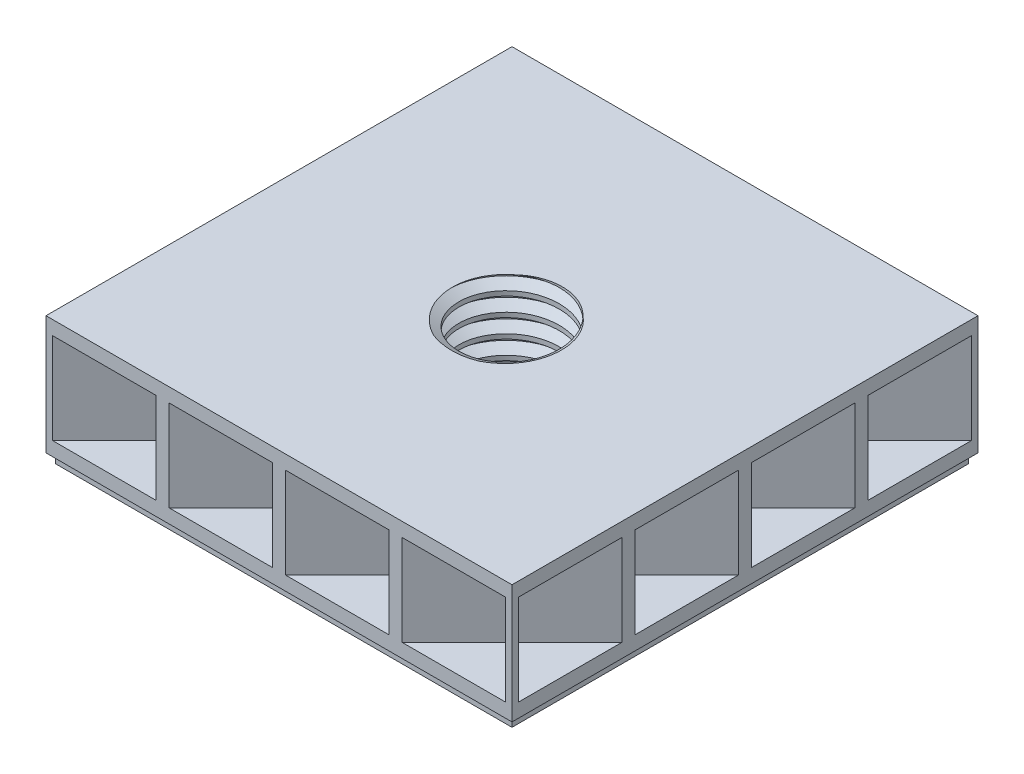
SolidWorks part; units mm, degrees
ref_plane "Front Plane" through (0, 0, 0) normal (0, 0, 1) x (1, 0, 0)
ref_plane "Top Plane" through (0, 0, 0) normal (0, 1, 0) x (1, 0, 0)
ref_plane "Right Plane" through (0, 0, 0) normal (1, 0, 0) x (0, 0, -1)
sketch "Sketch1" plane through (0, 0, 0) normal (0, 1, 0) x (1, 0, 0)
  line L0 (0, 20) -> (20, 0) construction
  line L1 (0, 0) -> (20, 0)
  line L2 (0, 0) -> (0, 20)
  line L3 (0, 20) -> (20, 20)
  line L4 (20, 0) -> (20, 20)
  circle A0 centre (10, 10) radius 2.157
  point P5 (10, 10)
  dimension "D3" = 4.314
  dimension "D1" = 20
  dimension "D2" = 20
extrude "Main Square" add sketch "Sketch1" along normal blind 5.5 contours L3 L0 A0 L4 | L0 L2 L1 A0
sketch "Sketch2" plane through (0, 0, 0) normal (0, 0, 1) x (1, 0, 0)
  line L0 (10, 5.5) -> (10, 0) construction
  line L1 (0, 0) -> (20, 0) construction
  line L3 (0, 0.4) -> (0.2, 0.4)
  line L4 (0, 5.5) -> (0, 0) construction
  line L5 (0.2, 0.4) -> (0.2, 0)
  line L6 (0.2, 0) -> (0, 0)
  line L7 (0, 0) -> (0, 0.4)
  line L8 (20, 0) -> (20, 0.4)
  line L9 (19.8, 0) -> (20, 0)
  line L10 (19.8, 0.4) -> (19.8, 0)
  line L11 (20, 0.4) -> (19.8, 0.4)
  point P2 (0, 0)
  point P3 (0, 0)
  point P4 (0, 0)
  point P5 (10, 0)
  point P17 (0, 0)
  point P18 (0, 0)
  point P19 (0, 0)
  point P20 (0, 0)
  point P21 (0, 0)
  point P22 (0, 0)
  dimension "D1" = 0.4
  dimension "D2" = 0.2
extrude "AntiWarpCuts1" cut sketch "Sketch2" against normal through all both and the other way through all
sketch "Sketch3" plane through (0, 0, 0) normal (-1, 0, 0) x (0, 0, 1)
  line L0 (-10, 5.5) -> (-10, 0) construction
  line L3 (-0.2, 0) -> (-0.2, 0.4)
  line L4 (-20, 0) -> (-19.8, 0)
  line L5 (-20, 0) -> (-20, 0.4)
  line L6 (-20, 0.4) -> (-19.8, 0.4)
  line L7 (-19.8, 0) -> (-19.8, 0.4)
  line L8 (0, 0.4) -> (-0.2, 0.4)
  line L9 (0, 0) -> (0, 0.4)
  line L10 (0, 0) -> (-0.2, 0)
  point P2 (0, 0)
  point P3 (-20, 0)
  point P4 (0, 0)
  point P5 (0, 0)
  point P15 (0, 0)
  dimension "D1" = 0.2
  dimension "D2" = 0.4
extrude "AntiWarpCuts2" cut sketch "Sketch3" against normal through all both and the other way through all
sketch "Sketch5" plane through (0, 0, 0) normal (-1, 0, 0) x (0, 0, 1)
  line L0 (-20, 5.5) -> (-20, 0.4) construction
  line L1 (-20, 4.9) -> (0, 4.9)
  line L2 (-20, 4.9) -> (-20, 1)
  line L3 (-20, 1) -> (0, 1)
  line L4 (0, 4.9) -> (0, 1)
  line L5 (0, 5.5) -> (0, 0.4) construction
  line L6 (0, 5.5) -> (-20, 5.5) construction
  line L7 (-20, 0.4) -> (0, 0.4) construction
  dimension "D1" = 0.6
  dimension "D2" = 0.6
extrude "NoFill" cut sketch "Sketch5" against normal through all both and the other way through all
sketch "Sketch6" plane through (0, 1, 0) normal (0, 1, 0) x (1, 0, 0)
  circle A0 centre (10, 10) radius 4
  circle A1 centre (10, 10) radius 2.157
  dimension "D1" = 8
extrude "ThreadMe" add sketch "Sketch6" along normal up to next contours A0
sketch "Sketch7" plane through (0, 4.9, 0) normal (0, -1, 0) x (1, 0, 0)
  line L0 (0, -5) -> (5, -5) construction
  line L1 (0, -20) -> (0, 0) construction
  line L2 (5, -5) -> (5, 0) construction
  line L3 (0, 0) -> (20, 0) construction
  line L4 (2.5, -2.5) -> (5, 0) construction
  line L5 (0, 0) -> (2.5, -2.5) construction
  line L6 (0.2828, 0) -> (2.5, -2.2172)
  line L7 (2.5, -2.2172) -> (4.7172, 0)
  line L8 (1.4777, -1.4777) -> (1.6191, -1.3363) construction
  line L9 (3.1231, -1.5941) -> (3.2645, -1.7355) construction
  line L10 (2.5, -2.5) -> (5, -2.5) construction
  line L11 (2.5, -2.5) -> (2.5, -5) construction
  line L12 (2.5, -2.7828) -> (4.7172, -5)
  line L13 (0.2828, -5) -> (2.5, -2.7828)
  line L14 (0, -0.2828) -> (2.2172, -2.5)
  line L15 (5, -0.2828) -> (2.7828, -2.5)
  line L16 (3.2645, -1.7355) -> (3.4059, -1.8769) construction
  line L17 (1.4777, -1.4777) -> (1.3363, -1.6191) construction
  line L18 (2.2172, -2.5) -> (2.5, -2.5) construction
  line L19 (5, -4.7172) -> (2.7828, -2.5)
  line L20 (0, -4.7172) -> (2.2172, -2.5)
  line L21 (2.2172, -2.5) -> (2.5, -2.2172) construction
  line L127 (5, -0.2828) -> (7.2172, -2.5)
  line L128 (5.2828, 0) -> (7.5, -2.2172)
  line L139 (7.5, -2.2172) -> (9.7172, 0)
  line L140 (10, -0.2828) -> (7.7828, -2.5)
  line L142 (0, 0) -> (0.2828, 0)
  line L143 (0, 0) -> (0, -0.2828)
  line L162 (10, -4.7172) -> (7.7828, -2.5)
  line L163 (7.5, -2.7828) -> (9.7172, -5)
  line L164 (5.2828, -5) -> (7.5, -2.7828)
  line L165 (5, -4.7172) -> (7.2172, -2.5)
  line L166 (10, -0.2828) -> (12.2172, -2.5)
  line L167 (10.2828, 0) -> (12.5, -2.2172)
  line L168 (12.5, -2.2172) -> (14.7172, 0)
  line L169 (15, -0.2828) -> (12.7828, -2.5)
  line L170 (15, -4.7172) -> (12.7828, -2.5)
  line L171 (12.5, -2.7828) -> (14.7172, -5)
  line L172 (10.2828, -5) -> (12.5, -2.7828)
  line L173 (10, -4.7172) -> (12.2172, -2.5)
  line L174 (15, -0.2828) -> (17.2172, -2.5)
  line L175 (15.2828, 0) -> (17.5, -2.2172)
  line L176 (17.5, -2.2172) -> (19.7172, 0)
  line L177 (20, -0.2828) -> (17.7828, -2.5)
  line L178 (20, -4.7172) -> (17.7828, -2.5)
  line L179 (17.5, -2.7828) -> (19.7172, -5)
  line L180 (15.2828, -5) -> (17.5, -2.7828)
  line L181 (15, -4.7172) -> (17.2172, -2.5)
  line L182 (5, -5.2828) -> (7.0337, -7.3165)
  line L183 (5.2828, -5) -> (7.3165, -7.0337)
  line L184 (8.37, -6.3472) -> (9.7172, -5)
  line L185 (10, -5.2828) -> (9.2025, -6.0803)
  line L188 (5.2828, -10) -> (6.0803, -9.2025)
  line L189 (5, -9.7172) -> (6.3472, -8.37)
  line L190 (10, -5.2828) -> (10.7975, -6.0803)
  line L191 (10.2828, -5) -> (11.63, -6.3472)
  line L192 (12.6835, -7.0337) -> (14.7172, -5)
  line L193 (15, -5.2828) -> (12.9663, -7.3165)
  line L194 (15, -9.7172) -> (13.6528, -8.37)
  line L195 (13.9197, -9.2025) -> (14.7172, -10)
  line L198 (15, -5.2828) -> (17.2172, -7.5)
  line L199 (15.2828, -5) -> (17.5, -7.2172)
  line L200 (17.5, -7.2172) -> (19.7172, -5)
  line L201 (20, -5.2828) -> (17.7828, -7.5)
  line L202 (20, -9.7172) -> (17.7828, -7.5)
  line L203 (17.5, -7.7828) -> (19.7172, -10)
  line L204 (15.2828, -10) -> (17.5, -7.7828)
  line L205 (15, -9.7172) -> (17.2172, -7.5)
  line L206 (5, -10.2828) -> (6.3472, -11.63)
  line L207 (5.2828, -10) -> (6.0803, -10.7975)
  line L210 (10, -14.7172) -> (9.2025, -13.9197)
  line L211 (8.37, -13.6528) -> (9.7172, -15)
  line L212 (5.2828, -15) -> (7.3165, -12.9663)
  line L213 (5, -14.7172) -> (7.0337, -12.6835)
  line L216 (13.9197, -10.7975) -> (14.7172, -10)
  line L217 (15, -10.2828) -> (13.6528, -11.63)
  line L218 (15, -14.7172) -> (12.7828, -12.5)
  line L219 (12.6835, -12.9663) -> (14.7172, -15)
  line L220 (10.2828, -15) -> (11.63, -13.6528)
  line L221 (10, -14.7172) -> (10.7975, -13.9197)
  line L222 (15, -10.2828) -> (17.2172, -12.5)
  line L223 (15.2828, -10) -> (17.5, -12.2172)
  line L224 (17.5, -12.2172) -> (19.7172, -10)
  line L225 (20, -10.2828) -> (17.7828, -12.5)
  line L226 (20, -14.7172) -> (17.7828, -12.5)
  line L227 (17.5, -12.7828) -> (19.7172, -15)
  line L228 (15.2828, -15) -> (17.5, -12.7828)
  line L229 (15, -14.7172) -> (17.2172, -12.5)
  line L230 (5, -15.2828) -> (7.2172, -17.5)
  line L231 (5.2828, -15) -> (7.5, -17.2172)
  line L232 (7.5, -17.2172) -> (9.7172, -15)
  line L233 (10, -15.2828) -> (7.7828, -17.5)
  line L234 (10, -19.7172) -> (7.7828, -17.5)
  line L235 (7.5, -17.7828) -> (9.7172, -20)
  line L236 (5.2828, -20) -> (7.5, -17.7828)
  line L237 (5, -19.7172) -> (7.2172, -17.5)
  line L238 (10, -15.2828) -> (12.2172, -17.5)
  line L239 (10.2828, -15) -> (12.5, -17.2172)
  line L240 (12.5, -17.2172) -> (14.7172, -15)
  line L241 (15, -15.2828) -> (12.7828, -17.5)
  line L242 (15, -19.7172) -> (12.7828, -17.5)
  line L243 (12.5, -17.7828) -> (14.7172, -20)
  line L244 (10.2828, -20) -> (12.5, -17.7828)
  line L245 (10, -19.7172) -> (12.2172, -17.5)
  line L246 (15, -15.2828) -> (17.2172, -17.5)
  line L247 (15.2828, -15) -> (17.5, -17.2172)
  line L248 (17.5, -17.2172) -> (19.7172, -15)
  line L249 (20, -15.2828) -> (17.7828, -17.5)
  line L250 (20, -19.7172) -> (17.7828, -17.5)
  line L251 (17.5, -17.7828) -> (19.7172, -20)
  line L252 (15.2828, -20) -> (17.5, -17.7828)
  line L253 (15, -19.7172) -> (17.2172, -17.5)
  line L254 (0, -5.2828) -> (2.2172, -7.5)
  line L255 (0.2828, -5) -> (2.5, -7.2172)
  line L256 (2.5, -7.2172) -> (4.7172, -5)
  line L257 (5, -5.2828) -> (2.7828, -7.5)
  line L258 (5, -9.7172) -> (2.7828, -7.5)
  line L259 (2.5, -7.7828) -> (4.7172, -10)
  line L260 (0.2828, -10) -> (2.5, -7.7828)
  line L261 (0, -9.7172) -> (2.2172, -7.5)
  line L262 (0, -10.2828) -> (2.2172, -12.5)
  line L263 (0.2828, -10) -> (2.5, -12.2172)
  line L264 (2.5, -12.2172) -> (4.7172, -10)
  line L265 (5, -10.2828) -> (2.7828, -12.5)
  line L266 (5, -14.7172) -> (2.7828, -12.5)
  line L267 (2.5, -12.7828) -> (4.7172, -15)
  line L268 (0.2828, -15) -> (2.5, -12.7828)
  line L269 (0, -14.7172) -> (2.2172, -12.5)
  line L270 (0, -15.2828) -> (2.2172, -17.5)
  line L271 (0.2828, -15) -> (2.5, -17.2172)
  line L272 (2.5, -17.2172) -> (4.7172, -15)
  line L273 (5, -15.2828) -> (2.7828, -17.5)
  line L274 (5, -19.7172) -> (2.7828, -17.5)
  line L275 (2.5, -17.7828) -> (4.7172, -20)
  line L276 (0.2828, -20) -> (2.5, -17.7828)
  line L277 (0, -19.7172) -> (2.2172, -17.5)
  line L278 (4.7172, 0) -> (5.2828, 0)
  line L279 (9.7172, 0) -> (10.2828, 0)
  line L280 (14.7172, 0) -> (15.2828, 0)
  line L281 (19.7172, 0) -> (20, 0)
  line L282 (20, 0) -> (20, -0.2828)
  line L283 (20, -4.7172) -> (20, -5.2828)
  line L284 (20, -9.7172) -> (20, -10.2828)
  line L285 (20, -14.7172) -> (20, -15.2828)
  line L286 (20, -15.2828) -> (20, -19.7172)
  line L287 (20, -20) -> (19.7172, -20)
  line L288 (14.7172, -20) -> (15.2828, -20)
  line L289 (4.7172, -20) -> (5.2828, -20)
  line L290 (0, -19.7172) -> (0, -20)
  line L291 (0, -20) -> (0.2828, -20)
  line L292 (0, -14.7172) -> (0, -15.2828)
  line L293 (0, -9.7172) -> (0, -10.2828)
  line L294 (0, -4.7172) -> (0, -5.2828)
  circle A0 centre (10, -10) radius 4
  dimension "D2" = 8
  dimension "D1" = 0.2
extrude "Lattice" add sketch "Sketch7" along normal up to surface (3.9 mm away)
thread "Thread1" pitch 0.8 start angle 0, offset 1, length 0, pitch 0.8, diameter 4.314
ref_plane "Plane1" through (12.157, -1, -10) normal (0, 0, 1) x (1, 0, 0)
sketch "Thread Profile1" plane through (12.157, -1, -10) normal (0, 0, 1) x (1, 0, 0)
  line L0 (0, 0) -> (0, 0.8) construction
  line L1 (0, 0) -> (0.433, 0.25)
  line L2 (0.433, 0.25) -> (0.433, 0.35)
  line L3 (0.433, 0.35) -> (0, 0.6)
  line L4 (0.433, 0.3) -> (0, 0.3) construction
  line L11 (0, 0) -> (0, 0.6)
  point P2 (0, 0)
  dimension "Pitch" = 0.8
  dimension "Profile_Angle" = 60
  dimension "Profile_Land" = 0.1
  dimension "Profile_Height" = 0.433
equation "\"D3@Sketch1\"=4.134+0.18"
